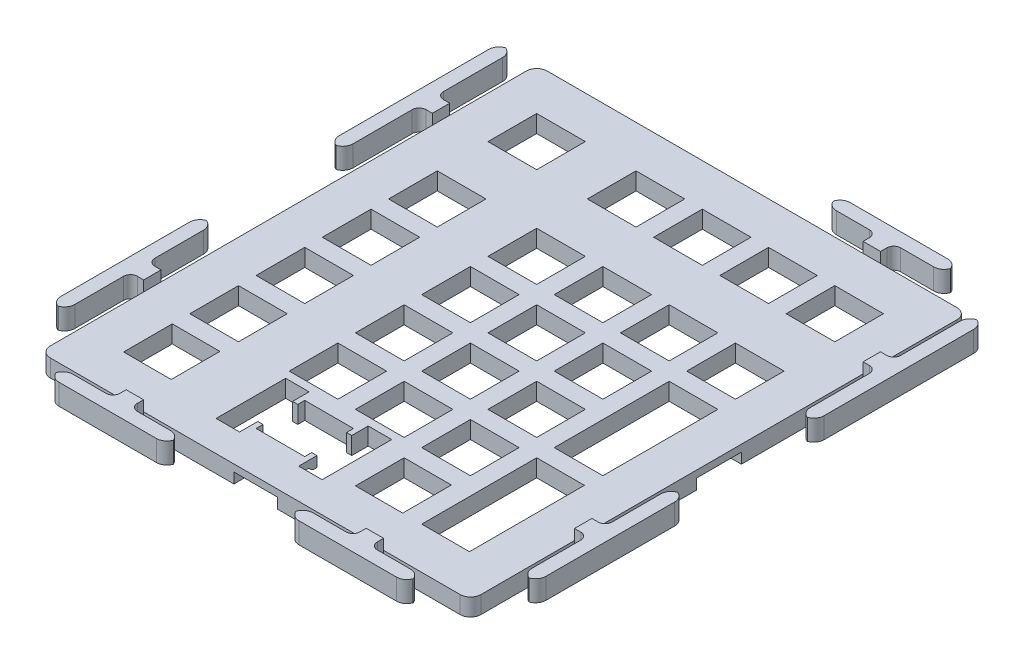
SolidWorks part; units mm, degrees
ref_plane "Front Plane" through (0, 0, 0) normal (0, 0, 1) x (1, 0, 0)
ref_plane "Top Plane" through (0, 0, 0) normal (0, 1, 0) x (1, 0, 0)
ref_plane "Right Plane" through (0, 0, 0) normal (1, 0, 0) x (0, 0, -1)
sketch "Sketch2" plane through (0, 0, 0) normal (0, 1, 0) x (1, 0, 0)
  line L0 (-50.856, -62.0444) -> (43.049, -62.0444)
  line L1 (-65.816, -47.0844) -> (-65.816, 65.8706)
  line L2 (-50.856, 80.8306) -> (43.049, 80.8306)
  line L3 (58.009, -47.0844) -> (58.009, 65.8706)
  line L4 (-65.816, -62.0444) -> (58.009, 80.8306) construction
  line L5 (-65.816, 80.8306) -> (58.009, -62.0444) construction
  line L6 (31.959, 54.7456) -> (45.959, 54.7456)
  line L7 (31.959, 54.7456) -> (31.959, 68.7456)
  line L8 (31.959, 68.7456) -> (45.959, 68.7456)
  line L9 (45.959, 54.7456) -> (45.959, 68.7456)
  line L10 (31.959, 54.7456) -> (45.959, 68.7456) construction
  line L11 (31.959, 68.7456) -> (45.959, 54.7456) construction
  line L12 (31.959, 61.7456) -> (26.909, 61.7456) construction
  line L13 (12.909, 54.7456) -> (26.909, 54.7456)
  line L14 (12.909, 54.7456) -> (12.909, 68.7456)
  line L15 (12.909, 68.7456) -> (26.909, 68.7456)
  line L16 (26.909, 54.7456) -> (26.909, 68.7456)
  line L17 (12.909, 61.7456) -> (7.859, 61.7456) construction
  line L18 (-6.141, 54.7456) -> (7.859, 54.7456)
  line L19 (-6.141, 54.7456) -> (-6.141, 68.7456)
  line L20 (-6.141, 68.7456) -> (7.859, 68.7456)
  line L21 (7.859, 54.7456) -> (7.859, 68.7456)
  line L22 (-6.141, 61.7456) -> (-11.191, 61.7456) construction
  line L23 (-25.191, 54.7456) -> (-11.191, 54.7456)
  line L24 (-25.191, 54.7456) -> (-25.191, 68.7456)
  line L25 (-25.191, 68.7456) -> (-11.191, 68.7456)
  line L26 (-11.191, 54.7456) -> (-11.191, 68.7456)
  line L27 (31.959, 26.1706) -> (45.959, 26.1706)
  line L28 (-53.766, 54.7456) -> (-39.766, 54.7456)
  line L29 (-53.766, 54.7456) -> (-53.766, 68.7456)
  line L30 (-53.766, 68.7456) -> (-39.766, 68.7456)
  line L31 (-39.766, 54.7456) -> (-39.766, 68.7456)
  line L32 (31.959, 26.1706) -> (31.959, 40.1706)
  line L33 (31.959, 40.1706) -> (45.959, 40.1706)
  line L34 (45.959, 26.1706) -> (45.959, 40.1706)
  line L35 (31.959, 26.1706) -> (45.959, 40.1706) construction
  line L36 (31.959, 40.1706) -> (45.959, 26.1706) construction
  line L37 (31.959, 33.1706) -> (26.909, 33.1706) construction
  line L38 (12.909, 26.1706) -> (26.909, 26.1706)
  line L39 (12.909, 26.1706) -> (12.909, 40.1706)
  line L40 (12.909, 40.1706) -> (26.909, 40.1706)
  line L41 (26.909, 26.1706) -> (26.909, 40.1706)
  line L42 (12.909, 33.1706) -> (7.859, 33.1706) construction
  line L43 (-6.141, 26.1706) -> (7.859, 26.1706)
  line L44 (-6.141, 26.1706) -> (-6.141, 40.1706)
  line L45 (-6.141, 40.1706) -> (7.859, 40.1706)
  line L46 (7.859, 26.1706) -> (7.859, 40.1706)
  line L47 (-6.141, 33.1706) -> (-11.191, 33.1706) construction
  line L48 (-25.191, 26.1706) -> (-11.191, 26.1706)
  line L49 (-25.191, 26.1706) -> (-25.191, 40.1706)
  line L50 (-25.191, 40.1706) -> (-11.191, 40.1706)
  line L51 (-11.191, 26.1706) -> (-11.191, 40.1706)
  line L52 (-53.766, 26.1706) -> (-39.766, 26.1706)
  line L53 (-53.766, 26.1706) -> (-53.766, 40.1706)
  line L54 (-53.766, 40.1706) -> (-39.766, 40.1706)
  line L55 (-39.766, 26.1706) -> (-39.766, 40.1706)
  line L56 (31.959, -11.9294) -> (45.959, -11.9294)
  line L57 (31.959, -11.9294) -> (31.959, 21.1206)
  line L58 (31.959, 21.1206) -> (45.959, 21.1206)
  line L59 (45.959, -11.9294) -> (45.959, 21.1206)
  line L60 (31.959, -11.9294) -> (45.959, 21.1206) construction
  line L61 (31.959, 21.1206) -> (45.959, -11.9294) construction
  line L62 (31.959, 4.5956) -> (26.909, 4.5956) construction
  line L63 (12.909, 7.1206) -> (26.909, 7.1206)
  line L64 (12.909, 7.1206) -> (12.909, 21.1206)
  line L65 (12.909, 21.1206) -> (26.909, 21.1206)
  line L66 (26.909, 7.1206) -> (26.909, 21.1206)
  line L67 (12.909, 14.1206) -> (7.859, 14.1206) construction
  line L68 (-6.141, 7.1206) -> (7.859, 7.1206)
  line L69 (-6.141, 7.1206) -> (-6.141, 21.1206)
  line L70 (-6.141, 21.1206) -> (7.859, 21.1206)
  line L71 (7.859, 7.1206) -> (7.859, 21.1206)
  line L72 (-6.141, 14.1206) -> (-11.191, 14.1206) construction
  line L73 (-25.191, 7.1206) -> (-11.191, 7.1206)
  line L74 (-25.191, 7.1206) -> (-25.191, 21.1206)
  line L75 (-25.191, 21.1206) -> (-11.191, 21.1206)
  line L76 (-11.191, 7.1206) -> (-11.191, 21.1206)
  line L77 (-53.766, 7.1206) -> (-39.766, 7.1206)
  line L78 (-53.766, 7.1206) -> (-53.766, 21.1206)
  line L79 (-53.766, 21.1206) -> (-39.766, 21.1206)
  line L80 (-39.766, 7.1206) -> (-39.766, 21.1206)
  line L85 (-65.816, 65.8706) -> (-65.816, 80.8306)
  line L88 (12.909, -11.9294) -> (26.909, -11.9294)
  line L89 (12.909, -11.9294) -> (12.909, 2.0706)
  line L90 (12.909, 2.0706) -> (26.909, 2.0706)
  line L91 (26.909, -11.9294) -> (26.909, 2.0706)
  line L92 (12.909, -4.9294) -> (7.859, -4.9294) construction
  line L93 (-6.141, -11.9294) -> (7.859, -11.9294)
  line L94 (-6.141, -11.9294) -> (-6.141, 2.0706)
  line L95 (-6.141, 2.0706) -> (7.859, 2.0706)
  line L96 (7.859, -11.9294) -> (7.859, 2.0706)
  line L97 (-6.141, -4.9294) -> (-11.191, -4.9294) construction
  line L98 (-25.191, -11.9294) -> (-11.191, -11.9294)
  line L99 (-25.191, -11.9294) -> (-25.191, 2.0706)
  line L100 (-25.191, 2.0706) -> (-11.191, 2.0706)
  line L101 (-11.191, -11.9294) -> (-11.191, 2.0706)
  line L102 (-53.766, -11.9294) -> (-39.766, -11.9294)
  line L103 (-53.766, -11.9294) -> (-53.766, 2.0706)
  line L104 (-53.766, 2.0706) -> (-39.766, 2.0706)
  line L105 (-39.766, -11.9294) -> (-39.766, 2.0706)
  line L112 (31.959, -50.0294) -> (45.6886, -50.0294)
  line L113 (12.909, -30.9794) -> (26.909, -30.9794)
  line L114 (12.909, -30.9794) -> (12.909, -16.9794)
  line L115 (12.909, -16.9794) -> (26.909, -16.9794)
  line L116 (26.909, -30.9794) -> (26.909, -16.9794)
  line L117 (12.909, -23.9794) -> (7.859, -23.9794) construction
  line L118 (-6.141, -30.9794) -> (7.859, -30.9794)
  line L119 (-6.141, -30.9794) -> (-6.141, -16.9794)
  line L120 (-6.141, -16.9794) -> (7.859, -16.9794)
  line L121 (7.859, -30.9794) -> (7.859, -16.9794)
  line L122 (-6.141, -23.9794) -> (-11.191, -23.9794) construction
  line L123 (-25.191, -30.9794) -> (-11.191, -30.9794)
  line L124 (-25.191, -30.9794) -> (-25.191, -16.9794)
  line L125 (-25.191, -16.9794) -> (-11.191, -16.9794)
  line L126 (-11.191, -30.9794) -> (-11.191, -16.9794)
  line L127 (-53.766, -30.9794) -> (-39.766, -30.9794)
  line L128 (-53.766, -30.9794) -> (-53.766, -16.9794)
  line L129 (-53.766, -16.9794) -> (-39.766, -16.9794)
  line L130 (-39.766, -30.9794) -> (-39.766, -16.9794)
  line L131 (-53.766, -50.0294) -> (-40.0588, -50.0294)
  line L132 (-53.766, -50.0294) -> (-53.766, -36.0294)
  line L133 (-53.766, -36.0294) -> (-40.0588, -36.0294)
  line L134 (-40.0588, -50.0294) -> (-40.0588, -36.0294)
  line L139 (12.909, -50.0294) -> (26.4811, -50.0294)
  line L140 (12.909, -50.0294) -> (12.909, -36.0294)
  line L141 (12.909, -36.0294) -> (26.4811, -36.0294)
  line L142 (26.4811, -50.0294) -> (26.4811, -36.0294)
  line L143 (31.959, -50.0294) -> (31.959, -16.9794)
  line L144 (31.959, -16.9794) -> (45.6886, -16.9794)
  line L145 (45.6886, -50.0294) -> (45.6886, -16.9794)
  line L146 (-65.816, 80.8306) -> (-50.856, 80.8306)
  line L147 (43.049, 80.8306) -> (58.009, 80.8306)
  line L148 (58.009, 80.8306) -> (58.009, 65.8706)
  line L149 (58.009, -47.0844) -> (58.009, -62.0444)
  line L150 (58.009, -62.0444) -> (43.049, -62.0444)
  line L151 (-50.856, -62.0444) -> (-65.816, -62.0444)
  line L152 (-65.816, -62.0444) -> (-65.816, -47.0844)
  line L153 (-15.666, -36.0294) -> (-1.666, -36.0294)
  line L154 (-1.666, -50.0294) -> (-15.666, -50.0294)
  line L155 (-1.666, -36.0294) -> (-1.666, -38.0294)
  line L156 (-1.666, -38.0294) -> (-0.166, -38.0294)
  line L157 (-0.166, -38.0294) -> (-0.166, -33.2794)
  line L158 (-0.166, -33.2794) -> (6.584, -33.2794)
  line L159 (6.584, -33.2794) -> (6.584, -53.2794)
  line L160 (6.584, -53.2794) -> (-0.166, -53.2794)
  line L161 (-0.166, -53.2794) -> (-0.166, -48.0294)
  line L162 (-0.166, -48.0294) -> (-1.666, -48.0294)
  line L163 (-1.666, -48.0294) -> (-1.666, -50.0294)
  line L164 (-15.666, -36.0294) -> (-15.666, -38.0294)
  line L165 (-17.166, -33.2794) -> (-17.166, -38.0294)
  line L166 (-17.166, -38.0294) -> (-15.666, -38.0294)
  line L167 (-17.166, -33.2794) -> (-23.916, -33.2794)
  line L168 (-23.916, -33.2794) -> (-23.916, -53.2794)
  line L169 (-23.916, -53.2794) -> (-17.166, -53.2794)
  line L170 (-17.166, -53.2794) -> (-17.166, -48.0294)
  line L171 (-17.166, -48.0294) -> (-15.666, -48.0294)
  line L172 (-15.666, -48.0294) -> (-15.666, -50.0294)
  line L173 (-8.666, -36.0294) -> (-8.666, -50.0294) construction
  point P0 (-3.9035, 9.3931)
  point P17 (38.959, 61.7456)
  point P40 (38.959, 33.1706)
  point P72 (-1.0487, -8.3316)
  point P73 (38.959, 4.5956)
  point P100 (-8.666, -43.0294)
  point P159 (-8.666, -43.0294)
  point P160 (0, 0)
  dimension "D63" = 14
  dimension "D1" = 123.825
  dimension "D2" = 142.875
  dimension "D3" = 14
  dimension "D4" = 14
  dimension "D5" = 5.05
  dimension "D6" = 5.05
  dimension "D7" = 5.05
  dimension "D8" = 14
  dimension "D9" = 14
  dimension "D10" = 14
  dimension "D11" = 14
  dimension "D12" = 14.575
  dimension "D13" = 14
  dimension "D14" = 14
  dimension "D15" = 5.05
  dimension "D16" = 5.05
  dimension "D17" = 5.05
  dimension "D18" = 14
  dimension "D19" = 14
  dimension "D20" = 14
  dimension "D21" = 14
  dimension "D22" = 12.085
  dimension "D23" = 12.05
  dimension "D24" = 14
  dimension "D25" = 14
  dimension "D26" = 14
  dimension "D27" = 14
  dimension "D28" = 14.575
  dimension "D29" = 14
  dimension "D30" = 14
  dimension "D31" = 14
  dimension "D32" = 14
  dimension "D33" = 14.575
  dimension "D34" = 14
  dimension "D35" = 33.05
  dimension "D36" = 5.05
  dimension "D37" = 5.05
  dimension "D38" = 5.05
  dimension "D39" = 14
  dimension "D40" = 14
  dimension "D41" = 14
  dimension "D42" = 14
  dimension "D43" = 14.575
  dimension "D44" = 14
  dimension "D45" = 14
  dimension "D46" = 14
  dimension "D47" = 14
  dimension "D48" = 5.05
  dimension "D49" = 33.05
  dimension "D50" = 5.05
  dimension "D51" = 5.05
  dimension "D52" = 5.05
  dimension "D53" = 5.05
  dimension "D54" = 14
  dimension "D55" = 14
  dimension "D56" = 14
  dimension "D57" = 14
  dimension "D58" = 14.575
  dimension "D59" = 14
  dimension "D60" = 14
  dimension "D61" = 14
  dimension "D62" = 14
  dimension "D64" = 1.5
  dimension "D65" = 2
  dimension "D66" = 5.05
  dimension "D67" = 5.05
  dimension "D68" = 14
  dimension "D69" = 14
  dimension "D70" = 14
  dimension "D71" = 14
  dimension "D72" = 5.05
  dimension "D73" = 5.05
  dimension "D74" = 14
  dimension "D75" = 5.05
  dimension "D76" = 0
  dimension "D77" = 14.575
  dimension "D78" = 14
  dimension "D81" = 20
  dimension "D82" = 4.75
  dimension "D83" = 5.25
  dimension "D84" = 30.5
extrude "Boss-Extrude1" add sketch "Sketch2" along normal blind 5
sketch "Sketch4" plane through (0, 5, 0) normal (0, 1, 0) x (1, 0, 0)
  line L0 (-3.9035, 87.6298) -> (-3.9035, -67.0539) construction
  line L1 (-68.78, 9.3931) -> (60.0523, 9.3931) construction
  line L2 (58.009, 80.8306) -> (2.509, 80.8306) construction
  line L3 (58.009, 80.8306) -> (-65.816, 80.8306) construction
  line L4 (-65.816, 80.8306) -> (-10.016, 80.8306) construction
  line L5 (-10.016, 80.8306) -> (-10.016, 76.3306)
  line L6 (-10.016, 76.3306) -> (2.509, 76.3306)
  line L7 (2.509, 76.3306) -> (2.509, 80.8306)
  line L8 (2.509, 80.8306) -> (-10.016, 80.8306)
  line L9 (58.009, -62.0444) -> (2.509, -62.0444) construction
  line L10 (-65.816, -62.0444) -> (58.009, -62.0444) construction
  line L11 (2.509, -62.0444) -> (2.509, -57.5444)
  line L12 (2.509, -57.5444) -> (-10.016, -57.5444)
  line L13 (-10.016, -57.5444) -> (-10.016, -62.0444)
  line L14 (-10.016, -62.0444) -> (2.509, -62.0444)
  line L15 (58.009, 80.8306) -> (58.009, 15.8306) construction
  line L16 (58.009, -62.0444) -> (58.009, 80.8306) construction
  line L17 (58.009, 15.8306) -> (53.509, 15.8306)
  line L18 (58.009, -62.0444) -> (58.009, 2.9556) construction
  line L19 (53.509, 15.8306) -> (53.509, 2.9556)
  line L20 (53.509, 2.9556) -> (58.009, 2.9556)
  line L21 (58.009, 2.9556) -> (58.009, 15.8306)
  line L22 (-65.816, 15.8306) -> (-61.316, 15.8306)
  line L23 (-65.816, 80.8306) -> (-65.816, -62.0444) construction
  line L24 (-61.316, 15.8306) -> (-61.316, 2.9556)
  line L25 (-61.316, 2.9556) -> (-65.816, 2.9556)
  line L26 (-65.816, 2.9556) -> (-65.816, 15.8306)
  dimension "D1" = 55.8
  dimension "55.5" = 55.5
  dimension "D2" = 4.5
  dimension "D3" = 4.5
  dimension "D4" = 65
  dimension "D5" = 4.5
  dimension "D6" = 65
  dimension "D7" = 4.5
extrude "Cut-Extrude1" cut sketch "Sketch4" against normal through all
sketch "Sketch5" plane through (0, 5, 0) normal (0, 1, 0) x (1, 0, 0)
  line L1 (-69.616, 55.8022) -> (-65.816, 55.8022)
  line L2 (28.009, -62.0444) -> (33.009, -62.0444)
  line L12 (33.0168, 84.6306) -> (47.5168, 84.6306)
  line L13 (47.5168, 84.6306) -> (47.5168, 88.6306)
  line L15 (28.0168, 84.6306) -> (13.5168, 84.6306)
  line L16 (13.5168, 84.6306) -> (13.5168, 88.6306)
  line L17 (13.5168, 88.6306) -> (47.5168, 88.6306)
  line L19 (58.009, -62.0444) -> (30.509, -62.0444) construction
  line L20 (2.509, -62.0444) -> (58.009, -62.0444) construction
  line L22 (-35.9908, -65.8444) -> (-21.4908, -65.8444)
  line L24 (-40.9908, -65.8444) -> (-55.4908, -65.8444)
  line L25 (-21.4908, -65.8444) -> (-21.4908, -69.8444)
  line L26 (-55.4908, -65.8444) -> (-55.4908, -69.8444)
  line L27 (-55.4908, -69.8444) -> (-21.4908, -69.8444)
  line L29 (33.009, -62.0444) -> (33.009, -65.8444)
  line L30 (33.009, -65.8444) -> (47.509, -65.8444)
  line L31 (28.009, -62.0444) -> (28.009, -65.8444)
  line L32 (28.009, -65.8444) -> (13.509, -65.8444)
  line L33 (47.509, -65.8444) -> (47.509, -69.8444)
  line L34 (13.509, -65.8444) -> (13.509, -69.8444)
  line L35 (13.509, -69.8444) -> (47.509, -69.8444)
  line L41 (-69.616, 50.8022) -> (-69.616, 28.8022)
  line L42 (-69.616, 28.8022) -> (-73.616, 28.8022)
  line L43 (-69.616, 55.8022) -> (-69.616, 77.8022)
  line L44 (-69.616, 77.8022) -> (-73.616, 77.8022)
  line L45 (-73.616, 77.8022) -> (-73.616, 28.8022)
  line L47 (-65.816, -27.1978) -> (-69.616, -27.1978)
  line L48 (-65.816, -32.1978) -> (-69.616, -32.1978)
  line L49 (-69.616, -32.1978) -> (-69.616, -51.1978)
  line L50 (-69.616, -51.1978) -> (-73.616, -51.1978)
  line L51 (-69.616, -27.1978) -> (-69.616, -8.1978)
  line L52 (-69.616, -8.1978) -> (-73.616, -8.1978)
  line L53 (-73.616, -8.1978) -> (-73.616, -51.1978)
  line L58 (61.809, 55.8306) -> (61.809, 77.8306)
  line L59 (61.809, 77.8306) -> (65.809, 77.8306)
  line L60 (61.809, 50.8306) -> (61.809, 28.8306)
  line L61 (61.809, 28.8306) -> (65.809, 28.8306)
  line L62 (65.809, 77.8306) -> (65.809, 28.8306)
  line L64 (58.009, -27.1444) -> (61.809, -27.1444)
  line L65 (58.009, -32.1444) -> (61.809, -32.1444)
  line L66 (61.809, -27.1444) -> (61.809, -8.1444)
  line L67 (61.809, -8.1444) -> (65.809, -8.1444)
  line L68 (61.809, -32.1444) -> (61.809, -51.1444)
  line L69 (61.809, -51.1444) -> (65.809, -51.1444)
  line L70 (65.809, -8.1444) -> (65.809, -51.1444)
  line L71 (27.5168, 80.8306) -> (33.5168, 80.8306) construction
  line L72 (-65.816, 55.8022) -> (-65.816, 50.8022)
  line L73 (-65.816, 50.8022) -> (-69.616, 50.8022)
  line L74 (-65.816, -62.0444) -> (-65.816, -29.6978) construction
  line L75 (58.009, 80.8306) -> (58.009, 53.3306) construction
  line L76 (58.009, 15.8306) -> (58.009, 80.8306) construction
  line L77 (61.809, 50.8306) -> (58.009, 50.8306)
  line L78 (28.0168, 84.6306) -> (28.0168, 80.8306)
  line L79 (28.0168, 80.8306) -> (33.0168, 80.8306)
  line L80 (33.0168, 80.8306) -> (33.0168, 84.6306)
  line L81 (58.009, 80.8306) -> (2.509, 80.8306) construction
  line L82 (58.009, 50.8306) -> (58.009, 55.8306)
  line L83 (58.009, -62.0444) -> (58.009, -29.6444) construction
  line L84 (58.009, 55.8306) -> (61.809, 55.8306)
  line L85 (-65.816, -27.1978) -> (-65.816, -32.1978)
  line L86 (-40.9908, -65.8444) -> (-40.9908, -62.0444)
  line L87 (-40.9908, -62.0444) -> (-35.9908, -62.0444)
  line L88 (-35.9908, -62.0444) -> (-35.9908, -65.8444)
  line L89 (-66.4832, -62.6978) -> (-38.4908, -62.0444) construction
  line L90 (-65.816, -62.0444) -> (-10.016, -62.0444) construction
  line L91 (-65.816, 80.8306) -> (-65.816, 53.3022) construction
  line L92 (-65.816, 80.8306) -> (-65.816, 15.8306) construction
  line L93 (-65.816, 2.9556) -> (-65.816, -62.0444) construction
  line L94 (58.009, -62.0444) -> (58.009, 2.9556) construction
  line L95 (58.009, -27.1444) -> (58.009, -32.1444)
  point P26 (-38.4908, -62.0444)
  point P51 (-65.816, 53.3022)
  point P52 (30.5168, 80.8306)
  point P71 (30.509, -62.0444)
  point P74 (58.009, 53.3306)
  point P86 (58.009, -29.6444)
  point P103 (-65.816, -29.6978)
  point P105 (30.5168, 80.8306)
  dimension "D5" = 3.8
  dimension "D6" = 5
  dimension "D7" = 14.5
  dimension "D8" = 4
  dimension "D9" = 5
  dimension "D10" = 3.8
  dimension "D11" = 14.5
  dimension "D12" = 4
  dimension "D13" = 5
  dimension "D14" = 3.8
  dimension "D15" = 14.5
  dimension "D16" = 4
  dimension "D17" = 3.8
  dimension "D18" = 5
  dimension "D19" = 22
  dimension "D20" = 4
  dimension "D21" = 5
  dimension "D22" = 3.8
  dimension "D23" = 19
  dimension "D24" = 4
  dimension "D25" = 27.5
  dimension "D26" = 5
  dimension "D27" = 22
  dimension "D28" = 4
  dimension "D29" = 5
  dimension "D30" = 3.8
  dimension "D31" = 19
  dimension "D32" = 4
  dimension "D33" = 28
  dimension "D34" = 27.5
  dimension "D36" = 6
  dimension "D37" = 0
  dimension "D38" = 32.4
  dimension "D39" = 3.8
extrude "Boss-Extrude2" add sketch "Sketch5" along normal mid plane 6
fillet "Fillet1" radius 3 4 edges at (47.5168, 5, -84.6306) (47.5168, 5, -88.6306) (13.5168, 5, -84.6306) (13.5168, 5, -88.6306)
fillet "Fillet2" radius 2 2 edges at (33.0168, 5, -84.6306) (28.0168, 5, -84.6306)
fillet "Fillet3" radius 2 2 edges at (61.809, 5, -50.8306) (61.809, 5, -55.8306)
sketch "Sketch6" plane through (0, 5, 0) normal (0, 1, 0) x (1, 0, 0)
  line L0 (53.509, 15.8306) -> (53.509, 2.9556)
  line L1 (53.509, 2.9556) -> (58.009, 2.9556)
  line L2 (58.009, 2.9556) -> (58.009, 15.8306)
  line L3 (58.009, 15.8306) -> (53.509, 15.8306)
  line L4 (-10.016, 76.3306) -> (2.509, 76.3306)
  line L5 (2.509, 76.3306) -> (2.509, 80.8306)
  line L6 (2.509, 80.8306) -> (-10.016, 80.8306)
  line L7 (-10.016, 80.8306) -> (-10.016, 76.3306)
  line L8 (-61.316, 15.8306) -> (-61.316, 2.9556)
  line L9 (-61.316, 2.9556) -> (-65.816, 2.9556)
  line L10 (-65.816, 2.9556) -> (-65.816, 15.8306)
  line L11 (-65.816, 15.8306) -> (-61.316, 15.8306)
  line L12 (-10.016, -62.0444) -> (2.509, -62.0444)
  line L13 (2.509, -62.0444) -> (2.509, -57.5444)
  line L14 (2.509, -57.5444) -> (-10.016, -57.5444)
  line L15 (-10.016, -57.5444) -> (-10.016, -62.0444)
extrude "Boss-Extrude3" add sketch "Sketch6" against normal blind 2
fillet "Fillet10" radius 3 4 edges at (65.809, 5, -77.8306) (61.809, 5, -77.8306) (65.809, 5, -28.8306) (61.809, 5, -28.8306)
fillet "Fillet13" radius 2 2 edges at (61.809, 5, 27.1444) (61.809, 5, 32.1444)
fillet "Fillet14" radius 3 4 edges at (61.809, 5, 51.1444) (65.809, 5, 51.1444) (65.809, 5, 8.1444) (61.809, 5, 8.1444)
fillet "Fillet15" radius 2 2 edges at (33.009, 5, 65.8444) (28.009, 5, 65.8444)
fillet "Fillet16" radius 3 4 edges at (47.509, 5, 69.8444) (47.509, 5, 65.8444) (13.509, 5, 69.8444) (13.509, 5, 65.8444)
fillet "Fillet17" radius 2 2 edges at (-40.9908, 5, 65.8444) (-35.9908, 5, 65.8444)
fillet "Fillet18" radius 3 4 edges at (-21.4908, 5, 69.8444) (-21.4908, 5, 65.8444) (-55.4908, 5, 69.8444) (-55.4908, 5, 65.8444)
fillet "Fillet19" radius 2 2 edges at (-69.616, 5, 27.1978) (-69.616, 5, 32.1978)
fillet "Fillet20" radius 3 4 edges at (-69.616, 5, 8.1978) (-73.616, 5, 8.1978) (-73.616, 5, 51.1978) (-69.616, 5, 51.1978)
fillet "Fillet22" radius 3 4 edges at (-73.616, 5, -28.8022) (-73.616, 5, -77.8022) (-69.616, 5, -77.8022) (-69.616, 5, -28.8022)
fillet "Fillet23" radius 2 2 edges at (-69.616, 5, -55.8022) (-69.616, 5, -50.8022)
fillet "Fillet24" radius 3 4 edges at (-65.816, 2.5, 62.0444) (58.009, 2.5, 62.0444) (58.009, 2.5, -80.8306) (-65.816, 2.5, -80.8306)
sketch "Sketch8" plane through (-0.166, 0, 0) normal (1, 0, 0) x (0, 0, -1)
  line L0 (-53.2794, 0) -> (-53.2794, 3)
  line L1 (-53.2794, 5) -> (-53.2794, 0) construction
  line L2 (-53.2794, 3) -> (-50.2794, 3)
  line L3 (-50.2794, 3) -> (-50.2794, 2)
  line L4 (-50.2794, 2) -> (-48.0294, 2)
  line L5 (-48.0294, 5) -> (-48.0294, 0) construction
  line L6 (-48.0294, 2) -> (-48.0294, 0)
  line L7 (-48.0294, 0) -> (-53.2794, 0)
  dimension "D1" = 3
  dimension "D2" = 3
  dimension "D3" = 2
extrude "Cut-Extrude2" cut sketch "Sketch8" against normal blind 20
fillet "Fillet25" radius 2 1 edges at (-8.666, 2, 50.2794)
